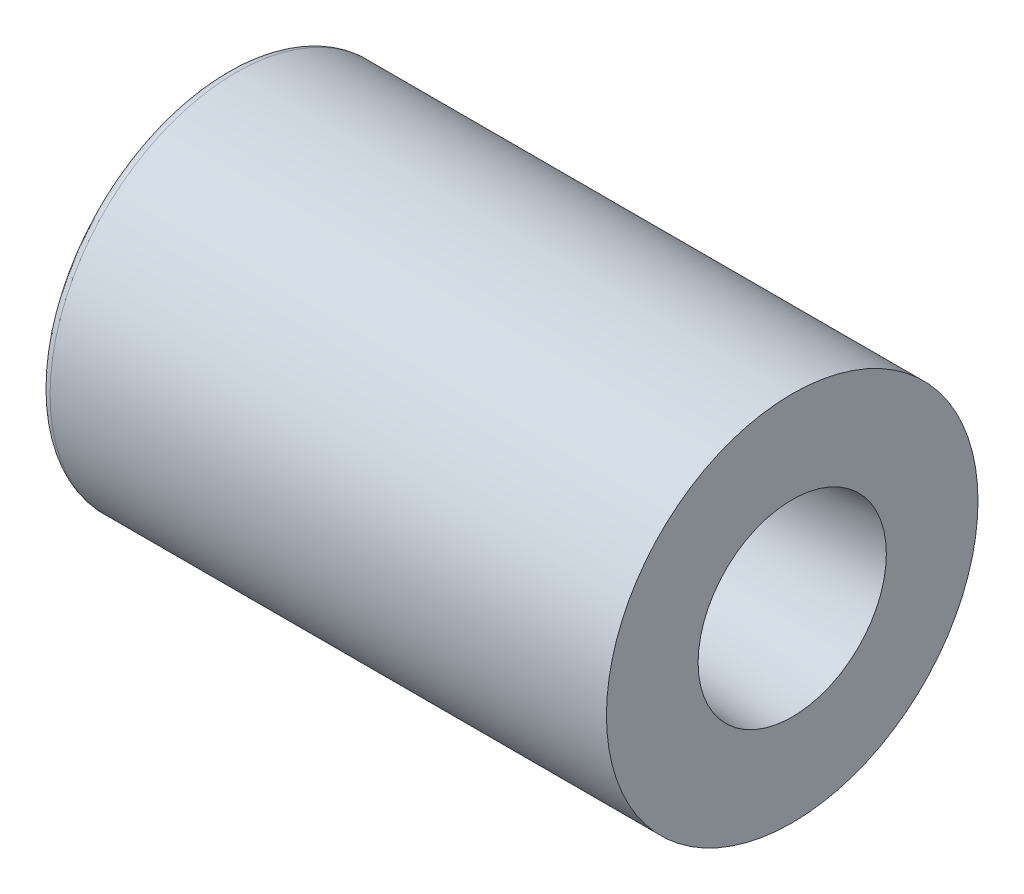
SolidWorks part; units mm, degrees
ref_plane "Front Plane" through (0, 0, 0) normal (0, 0, 1) x (1, 0, 0)
ref_plane "Top Plane" through (0, 0, 0) normal (0, 1, 0) x (1, 0, 0)
ref_plane "Right Plane" through (0, 0, 0) normal (1, 0, 0) x (0, 0, -1)
sketch "Sketch1" plane through (0, 0, 0) normal (0, 1, 0) x (1, 0, 0)
  line L0 (0, 0) -> (0, 2.286) construction
  line L1 (0, 2.286) -> (0, 5.3848)
  line L2 (0, 9.525) -> (29.0323, 9.525)
  line L3 (29.0323, 9.525) -> (29.0323, 4.826)
  line L4 (29.0323, 4.826) -> (0, 2.286)
  line L5 (0, 0) -> (29.0323, 0) construction
  line L6 (29.0323, 0) -> (29.0323, 4.826) construction
  line L7 (0, 5.3848) -> (1.905, 5.3848)
  line L8 (1.905, 5.3848) -> (1.905, 8.001)
  line L9 (1.905, 8.001) -> (0, 8.001)
  line L10 (0, 8.001) -> (0, 9.525)
  dimension "D1" = 2.286
  dimension "D2" = 4.826
  dimension "D3" = 5
  dimension "D4" = 9.525
  dimension "D5" = 5.3848
  dimension "D6" = 8.001
  dimension "D7" = 1.905
revolve "Revolve1" add sketch "Sketch1" angle 360 about L5
fillet "Fillet1" radius 0.508 1 edges at (0, 0, 9.525)
equation "\"z\" = 8\t\t\t\t'number of blades"
equation "\"de\" = 0.43in\t\t\t'entrance eye diameter"
equation "\"de_length\" = 10mm\t\t'entrance eye consistent length"
equation "\"d_exit\" = 0.18in \t\t'throat aka d1"
equation "\"d2\" = 2.1in \t\t\t'outer diameter of the impeller"
equation "\"b2\" = .2in\t\t\t'tip height from disc surface at d2; slightly higher than d_exit"
equation "\"b1\" = \"b2\" + (\"d2\"/2 - \"de\"/2)*tan(\"theta\") \t\t\t'tip height from disc surface at inlet eye"
equation "\"theta\" = 12\t\t\t'angle of blades from inner to outer "
equation "\"ae\" = 3.14*(\"de\"^2)/4\t\t'entrance eye area'"
equation "\"ce\" = 3.14*\"de\"\t\t'entrance eye circumference"
equation "\"av_ratio\" = .325\t\t'ratio of av/ae at N_s of 470, range is .275 to .375, .325 ideal. High ratio means bigger area means smaller blades"
equation "\"av\" = \"ae\"*\"av_ratio\"\t\t'area between just two blades"
equation "\"s_open\" = \"av\"/\"b1\"\t\t'width of open area"
equation "\"s\"=\"ce\" - \"z\"*\"s_open\""
equation "\"min blade thickness\" = .15in"
equation "\"bearing OD\" = 30mm"
equation "\"bearing ID\"= 10mm"
equation "\"bearing depth\"= 9mm"
equation "\"bearing outer race thickness\"= 1mm"
equation "\"bearing inner race thickness\"= 1mm"
equation "\"bearing bore\" = \"bearing depth\" + 1mm"
equation "\"lower seal OD\" = .917in\t\t'this is https://www.mcmaster.com/#9281k121/=174001b"
equation "\"lower seal ID\"= .375in"
equation "\"lower seal depth\" = .625in + .218in"
equation "\"lower seal bore\" = \"lower seal depth\" + 1mm"
equation "\"upper seal OD\" = 1.125in\t'this is https://www.mcmaster.com/#5154t33/=173zuau, needs to be visually inspected before machining!"
equation "\"upper seal ID\"= 0.625in"
equation "\"upper seal depth\"= .25in\t'aka height; these values need to be confirmed by inspection!! We may want to compress the height."
equation "\"upper seal bore\" = \"upper seal depth\" + 1mm"
equation "\"big o-ring thickness\" = .139in"
equation "\"big o-ring OD\" = 2.734in"
equation "\"big o-ring ID\" = 3.012in"
equation "\"big o-ring groove depth\" = \"big o-ring thickness\"*4/5"
equation "\"impeller center height\" = \"impeller base thickness\" + \"b1\"\t'impeller height at de"
equation "\"impeller outer height\" = \"impeller base thickness\" + \"b2\"\t'impeller height at de"
equation "\"impeller upper clearance\"= .5mm"
equation "\"impeller horizontal clearance\"= (\"d2\"*1.15 - \"d2\")/2 \t\t'clearance based on D2-D3 ratio for circular volute, ranges 1.15 to 1.2"
equation "\"impeller bottom clearance\"= .5mm"
equation "\"impeller base thickness\"= 2mm"
equation "\"impeller dowel diameter\" = 2mm"
equation "\"impeller bolt head diameter\" = \"m4 head bore diameter\""
equation "\"impeller bolt head depth\" = 4mm"
equation "\"impeller bolt stop depth\" = 3mm"
equation "\"impeller bolt bore\" = \"m4 clearance\""
equation "\"impeller shaft bore depth\" = 12mm"
equation "\"impeller shaft bore\" = 8mm"
equation "\"impeller boss depth\" = \"impeller shaft bore depth\"+\"impeller bolt stop depth\"+\"impeller bolt head depth\"-\"impeller base thickness\""
equation "\"impeller boss diameter\" = \"upper seal ID\""
equation "\"impeller dowel length\" = 2mm*2 + \"impeller shaft bore\""
equation "\"coupler motor shaft hole ID\"= 8mm"
equation "\"coupler OD\"= 17mm"
equation "\"coupler length\"= 25mm"
equation "\"motor OD\" = 64mm"
equation "\"motor shaft diameter\"= 8mm"
equation "\"motor shaft pride\"= 32mm"
equation "\"motor to bearing plate distance\" = \"motor shaft pride\" + 2mm +\"coupler length\"/2"
equation "\"square plate bolt bore\" = \"m8 clearance\""
equation "\"square plate bolt head diameter\" = 13.5mm"
equation "\"square plate bolt head depth\" = 8mm"
equation "\"square plate bolt pattern diameter\"= 3.5in"
equation "\"motor mount center bore\"= \"coupler OD\"+ 4mm"
equation "\"motor mount post radius\"= ( 3 * \"square plate bolt bore\" ) / 2"
equation "\"motor mount m4 screw hole diameter\"= 4mm"
equation "\"motor mount m4 head diameter\"= 7.25mm"
equation "\"motor mount m4 head depth\"= 4mm"
equation "\"motor mount m4 pattern diamater\" = 30mm"
equation "\"motor mount plate thickness\"= 8mm + \"motor mount m4 head depth\""
equation "\"bearing plate stop ID\" = \"bearing OD\" - 4mm"
equation "\"bearing plate stop depth\" = 3mm"
equation "\"bearing plate thickness\" = \"bearing bore\" + \"bearing plate stop depth\" + \"shaft bearing stop length\""
equation "\"lower seal plate lip depth\" = 2mm"
equation "\"lower seal plate lip ID\" = \"lower seal OD\" - 3mm"
equation "\"lower seal plate thickness\" = \"lower seal plate lip depth\" + \"lower seal bore\""
equation "\"shaft coupler section diameter\" = 8mm"
equation "\"shaft coupler section length\" = \"motor to bearing plate distance\" - \"motor shaft pride\" - 2mm"
equation "\"shaft bearing section diameter\" = \"bearing ID\""
equation "\"shaft bearing section length\" = \"bearing plate stop depth\" + \"bearing depth\""
equation "\"shaft bearing stop diameter\" = \"bearing ID\" + 4mm"
equation "\"shaft bearing stop length\" = 3mm"
equation "\"shaft lower seal section diameter\" = \"lower seal ID\""
equation "\"shaft lower seal section length\" = \"lower seal plate thickness\" + 1mm"
equation "\"shaft impeller section diameter\" = \"impeller shaft bore\""
equation "\"shaft impeller section length\" = \"upper seal plate thickness\" + \"upper seal plate riser\" + \"impeller bottom clearance\" + \"impeller base thickness\" - \"impeller bolt head depth\" - \"impeller bolt stop depth\""
equation "\"upper seal plate thickness\" = \"upper seal plate pressure hole diameter\"+10mm"
equation "\"upper seal plate lip ID\" = \"upper seal OD\" - 3mm"
equation "\"upper seal plate riser\" = 6.59mm \t\t'this number needs to be read from the housing file"
equation "\"upper seal plate pressure hole diameter\" = .125in\t'this is 1/8 drill "
equation "\"upper seal plate pressure tap diameter\" = .328125in \t'this is 21/64 drill for a 1/8 ANPT tap"
equation "\"upper seal plate pressure tap grip\" = 5mm\t\t'this is the area around the tap so it doesn't crack"
equation "\"upper seal plate pressure tap depth\" = 12"
equation "\"impeller cavity center height\"= \"impeller bottom clearance\" + \"impeller upper clearance\" + \"impeller center height\""
equation "\"impeller cavity diameter\"= 2 * \"impeller horizontal clearance\" + \"d2\" \t\t\t\t\t\t\t\t\t'called D3 analytically"
equation "\"impeller cavity outer height\"= \"impeller bottom clearance\" + \"impeller upper clearance\" + \"impeller base thickness\" + \"b2\" \t\t'this is height at impeller diameter d2, not at d3"
equation "\"impeller housing thickness\"= \"impeller housing exit threaded diameter\" + 2*\"impeller housing outlet grip\""
equation "\"impeller housing diameter\" = \"square plate bolt pattern diameter\" + 2*\"motor mount post radius\""
equation "\"impeller housing bolt count\" = 8"
equation "\"impeller housing bolt diameter\" = \"m6 clearance\""
equation "\"impeller housing bolt pattern diameter\" = 3.5in"
equation "\"impeller housing threaded inlet diameter\" = 0.515625in \t'this is the 33/64 drill size for 9/16-18 fitting, expecting swagelok SS-8FK0-1-6STH fitting"
equation "\"impeller housing threaded inlet depth\"= 10mm"
equation "\"impeller housing exit threaded diameter\"= 0.515625in \t\t'this is the 33/64 drill size for 9/16-18 fitting, expecting swagelok SS-8FK0-1-6STH fitting"
equation "\"impeller housing exit threaded depth\"= 10mm"
equation "\"impeller housing diffuser conical angle\"=10"
equation "\"impeller housing diffuser tangent angle\"=5"
equation "\"impeller housing diffuser final diameter\" = .38in\t\t'aka d2'"
equation "\"impeller housing outlet grip\" = 5mm"
equation "\"end mill size\" = 0.375in\t'for 3/8 endmill"
equation "\"m4 clearance\" = 0.171875in \t'this is 11/64 bit for 4.36mm"
equation "\"m4 tap\" = 0.125in\t\t'this is 1/8 bit for 3.17mm"
equation "\"m4 head bore diameter\" = 7.5mm"
equation "\"m4 head bore depth\" = 5mm\t'actual is ~4mm"
equation "\"m6 clearance\" = 0.234375in\t'this is 15/64 bit = 5.95mm, could use 6mm bit, B bit for 6.04mm or 1/4 bit for 6.35mm"
equation "\"m6 tap\" = 5mm\t\t\t'5mm is appropriate, could use 13/64 or #5,6,7"
equation "\"m6 head bore diameter\" = 11mm\t\t"
equation "\"m6 head bore depth\" = 7mm\t'actual is 6mm"
equation "\"m8 clearance\" = 0.3125in\t'this is 5/16in for 7.93mm, could use 8mm, O,P, or 21/64"
equation "\"m8 tap\" = 0.265625in\t\t'this is 17/64 for 6.746875mm"
equation "\"m8 head bore diameter\" = 14mm"
equation "\"m8 head bore depth\" = 9mm\t'actual is 8mm"
equation "\"D1@Sketch1\"=\"d_exit\"/2"
equation "\"D2@Sketch1\"=\"impeller housing diffuser final diameter\"/2"
equation "\"diffuser cartridge OD\" =.75in"
equation "\"D4@Sketch1\"=\"diffuser cartridge OD\"/2"
